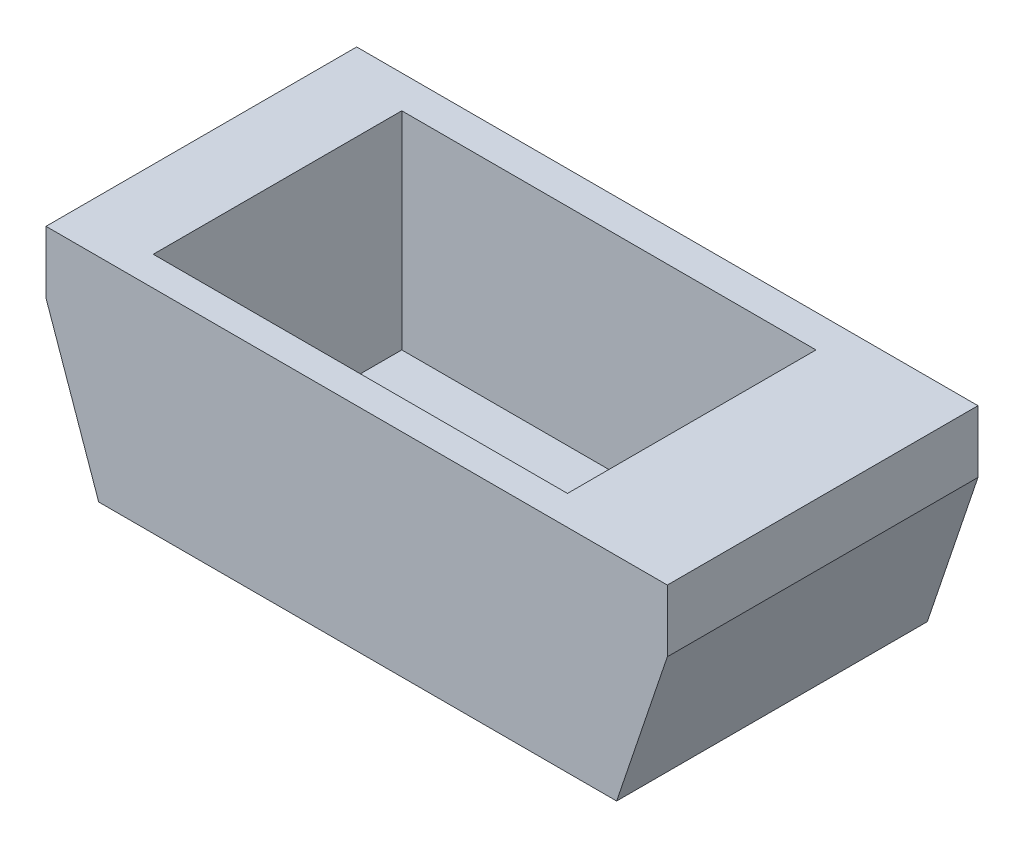
SolidWorks part; units mm, degrees
ref_plane "Front Plane" through (0, 0, 0) normal (0, 0, 1) x (1, 0, 0)
ref_plane "Top Plane" through (0, 0, 0) normal (0, 1, 0) x (1, 0, 0)
ref_plane "Right Plane" through (0, 0, 0) normal (1, 0, 0) x (0, 0, -1)
sketch "Sketch1" plane through (0, 0, 0) normal (0, 0, 1) x (1, 0, 0)
  line L0 (-49.7914, 32.6453) -> (-19.7914, 32.6453)
  line L1 (-19.7914, 32.6453) -> (-19.7914, 29.6453)
  line L2 (-49.7914, 32.6453) -> (-49.7914, 29.6453)
  line L6 (-47.2477, 22.3886) -> (-22.239, 22.3886)
  line L8 (-49.7914, 29.6453) -> (-47.2477, 22.3886)
  line L9 (-19.7914, 29.6453) -> (-22.239, 22.3886)
extrude "Boss-Extrude1" add sketch "Sketch1" along normal blind 15
sketch "Sketch2" plane through (0, 32.6453, 0) normal (0, 1, 0) x (1, 0, 0)
sketch "Sketch3" plane through (0, 32.6453, 0) normal (0, 1, 0) x (1, 0, 0)
  line L1 (-49.7914, 0) -> (-19.7914, 0)
  line L2 (-49.7914, 0) -> (-49.7914, -15)
  line L3 (-49.7914, -15) -> (-19.7914, -15)
  line L4 (-19.7914, 0) -> (-19.7914, -15)
  point P6 (-49.7914, -15)
sketch "Sketch4" plane through (0, 32.6453, 0) normal (0, 1, 0) x (1, 0, 0)
  line L1 (-46.0331, -1.5798) -> (-26.0331, -1.5798)
  line L2 (-46.0331, -1.5798) -> (-46.0331, -13.5798)
  line L3 (-46.0331, -13.5798) -> (-26.0331, -13.5798)
  line L4 (-26.0331, -1.5798) -> (-26.0331, -13.5798)
extrude "Cut-Extrude2" cut sketch "Sketch4" against normal blind 10
